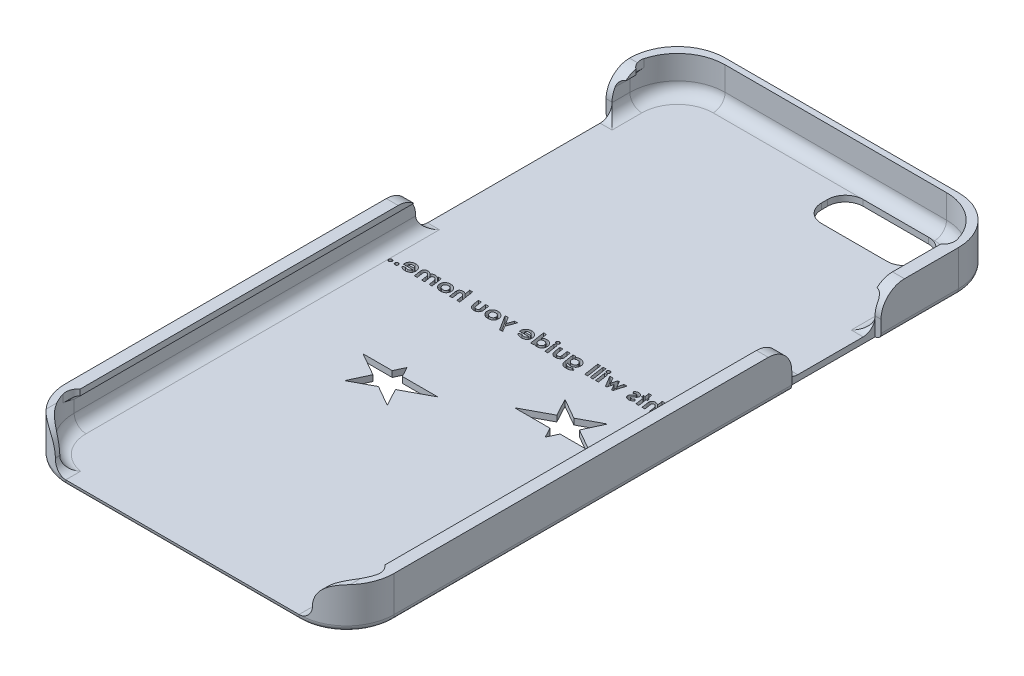
SolidWorks part; units mm, degrees
ref_plane "Front Plane" through (0, 0, 0) normal (0, 0, 1) x (1, 0, 0)
ref_plane "Top Plane" through (0, 0, 0) normal (0, 1, 0) x (1, 0, 0)
ref_plane "Right Plane" through (0, 0, 0) normal (1, 0, 0) x (0, 0, -1)
sketch "Sketch1" plane through (0, 0, 0) normal (0, 1, 0) x (1, 0, 0)
  line L1 (-35.052, 70.358) -> (35.052, 70.358)
  line L2 (-35.052, 70.358) -> (-35.052, -70.358)
  line L3 (-35.052, -70.358) -> (35.052, -70.358)
  line L4 (35.052, 70.358) -> (35.052, -70.358)
  line L5 (-35.052, 70.358) -> (35.052, -70.358) construction
  line L6 (-35.052, -70.358) -> (35.052, 70.358) construction
  point P0 (0, 0)
  dimension "D1" = 70.104
  dimension "D2" = 140.716
extrude "Boss-Extrude1" add sketch "Sketch1" along normal blind 1.27
sketch "Sketch2" plane through (0, 1.27, 0) normal (0, 1, 0) x (1, 0, 0)
  line L0 (-35.052, -70.358) -> (0, -70.358)
  line L1 (-35.052, -70.358) -> (35.052, -70.358) construction
  line L2 (-35.052, 70.358) -> (-35.052, -70.358)
  line L3 (-35.052, 70.358) -> (35.052, 70.358)
  line L4 (-33.782, 69.088) -> (-33.782, -69.088)
  line L5 (0, -70.358) -> (35.052, -70.358)
  line L6 (-33.782, -69.088) -> (33.782, -69.088)
  line L7 (35.052, 70.358) -> (35.052, -70.358)
  line L9 (33.782, 69.088) -> (33.782, -69.088)
  line L12 (-33.782, 69.088) -> (33.782, 69.088)
  dimension "D1" = 1.27
  dimension "D2" = 1.27
  dimension "D3" = 1.27
  dimension "D5" = 1.27
extrude "Boss-Extrude2" add sketch "Sketch2" along normal blind 7.62
sketch "Sketch3" plane through (-35.052, 0, 0) normal (-1, 0, 0) x (0, 0, 1)
  line L0 (-70.358, 8.89) -> (70.358, 8.89) construction
  line L1 (-55.118, 8.89) -> (-13.208, 8.89)
  line L2 (-55.118, 8.89) -> (-55.118, 1.27)
  line L3 (-55.118, 1.27) -> (-13.208, 1.27)
  line L4 (-13.208, 8.89) -> (-13.208, 1.27)
  line L5 (-70.358, 8.89) -> (-70.358, 0) construction
  line L6 (-70.358, 0) -> (70.358, 0) construction
  dimension "D1" = 15.24
  dimension "D2" = 57.15
  dimension "D3" = 1.27
extrude "Cut-Extrude1" cut sketch "Sketch3" against normal blind 1.27
sketch "Sketch5" plane through (35.052, 0, 0) normal (1, 0, 0) x (0, 0, -1)
  line L0 (-70.358, 8.89) -> (70.358, 8.89) construction
  line L1 (24.638, 8.89) -> (43.688, 8.89)
  line L2 (24.638, 8.89) -> (24.638, 1.27)
  line L3 (24.638, 1.27) -> (43.688, 1.27)
  line L4 (43.688, 8.89) -> (43.688, 1.27)
  line L5 (70.358, 8.89) -> (70.358, 0) construction
  line L6 (-70.358, 0) -> (70.358, 0) construction
  dimension "D1" = 26.67
  dimension "D2" = 45.72
  dimension "D3" = 1.27
extrude "Cut-Extrude2" cut sketch "Sketch5" against normal blind 1.27
sketch "Sketch6" plane through (0, 0, 70.358) normal (0, 0, 1) x (1, 0, 0)
  line L1 (-35.052, 8.89) -> (35.052, 8.89) construction
  line L2 (-27.432, 8.89) -> (27.432, 8.89)
  line L3 (-27.432, 8.89) -> (-27.432, 1.27)
  line L4 (-27.432, 1.27) -> (27.432, 1.27)
  line L8 (27.432, 8.89) -> (27.432, 1.27)
  line L9 (-35.052, 8.89) -> (-35.052, 0) construction
  line L10 (35.052, 8.89) -> (35.052, 0) construction
  line L11 (-35.052, 0) -> (35.052, 0) construction
  dimension "D1" = 7.62
  dimension "D2" = 7.62
  dimension "D3" = 1.27
extrude "Cut-Extrude3" cut sketch "Sketch6" against normal blind 1.27
sketch "Sketch7" plane through (0, 0, 0) normal (0, -1, 0) x (1, 0, 0)
  line L0 (35.052, 70.358) -> (35.052, -70.358) construction
  line L1 (26.162, -57.658) -> (4.572, -57.658)
  line L2 (26.162, -57.658) -> (26.162, -66.548)
  line L3 (26.162, -66.548) -> (4.572, -66.548)
  line L4 (4.572, -57.658) -> (4.572, -66.548)
  line L5 (35.052, -70.358) -> (-35.052, -70.358) construction
  dimension "D1" = 8.89
  dimension "D2" = 30.48
  dimension "D3" = 3.81
  dimension "D4" = 12.7
extrude "Cut-Extrude4" cut sketch "Sketch7" against normal blind 1.27
fillet "Fillet1" radius 10.16 4 edges at (33.782, 5.08, -69.088) (-33.782, 5.08, -69.088) (-33.782, 5.08, 69.088) (33.782, 5.08, 69.088)
fillet "Fillet2" radius 10.16 4 edges at (-35.052, 4.445, -70.358) (35.052, 4.445, -70.358) (35.052, 4.445, 70.358) (-35.052, 4.445, 70.358)
sketch "Sketch8" plane through (-33.782, 0, 0) normal (1, 0, 0) x (0, 0, -1)
  line L0 (58.928, 1.27) -> (58.928, 8.89) construction
  line L1 (55.118, 8.89) -> (58.928, 8.89)
  line L2 (55.118, 8.89) -> (55.118, 7.62)
  line L3 (55.118, 7.62) -> (58.928, 7.62)
  line L4 (58.928, 8.89) -> (58.928, 7.62)
  dimension "D1" = 1.27
extrude "Boss-Extrude3" add sketch "Sketch8" along normal blind 1.27
sketch "Sketch13" plane through (0, 0, -69.088) normal (0, 0, 1) x (1, 0, 0)
  line L0 (23.622, 1.27) -> (23.622, 8.89) construction
  line L1 (-23.622, 8.89) -> (23.622, 8.89)
  line L2 (-23.622, 8.89) -> (-23.622, 7.62)
  line L3 (-23.622, 7.62) -> (23.622, 7.62)
  line L4 (23.622, 8.89) -> (23.622, 7.62)
  dimension "D1" = 1.27
extrude "Boss-Extrude6" [suppressed] add sketch "Sketch13" along normal blind 1.27
sketch "Sketch14" plane through (33.782, 0, 0) normal (-1, 0, 0) x (0, 0, 1)
  line L0 (-43.688, 1.27) -> (-43.688, 8.89) construction
  line L1 (-58.928, 8.89) -> (-43.688, 8.89)
  line L2 (-58.928, 8.89) -> (-58.928, 7.62)
  line L3 (-58.928, 7.62) -> (-43.688, 7.62)
  line L4 (-43.688, 8.89) -> (-43.688, 7.62)
  dimension "D1" = 1.27
extrude "Boss-Extrude7" add sketch "Sketch14" along normal blind 1.27
sketch "Sketch19" plane through (33.782, 0, 0) normal (-1, 0, 0) x (0, 0, 1)
  line L1 (59.6694, 1.27) -> (59.6694, 8.89) construction
  line L2 (-24.638, 8.89) -> (59.6694, 8.89)
  line L3 (-24.638, 8.89) -> (-24.638, 7.62)
  line L4 (-24.638, 7.62) -> (59.6694, 7.62)
  line L5 (59.6694, 8.89) -> (59.6694, 7.62)
  dimension "D1" = 1.27
extrude "Boss-Extrude8" add sketch "Sketch19" along normal blind 1.27
sketch "Sketch20" plane through (-33.782, 0, 0) normal (1, 0, 0) x (0, 0, -1)
  line L1 (-59.6694, 8.89) -> (-59.6694, 1.27) construction
  line L2 (13.208, 8.89) -> (-59.6694, 8.89)
  line L3 (13.208, 8.89) -> (13.208, 7.62)
  line L4 (13.208, 7.62) -> (-59.6694, 7.62)
  line L5 (-59.6694, 8.89) -> (-59.6694, 7.62)
  dimension "D1" = 1.27
extrude "Boss-Extrude9" add sketch "Sketch20" along normal blind 1.27
fillet "Fillet9" radius 3.81 4 edges at (26.162, 0.635, -57.658) (26.162, 0.635, -66.548) (4.572, 0.635, -66.548) (4.572, 0.635, -57.658)
fillet "Fillet12" radius 1.27 8 edges at (32.0762, 0, 67.3822) (0, 0, 70.358) (-32.0762, 0, 67.3822) (-35.052, 0, 0) (-32.0762, 0, -67.3822) (0, 0, -70.358) (32.0762, 0, -67.3822) (35.052, 0, 0)
fillet "Fillet16" radius 2.54 9 edges at (33.782, 1.27, -51.308) (30.8062, 1.27, -66.1122) (-33.782, 1.27, -57.023) (-30.8062, 1.27, -66.1122) (33.782, 1.27, 17.5157) (-33.782, 1.27, 23.2307) (0, 1.27, -69.088) (32.0462, 1.27, 65.349) (-32.0462, 1.27, 65.349)
sketch "Sketch28" plane through (0, 1.27, 0) normal (0, 1, 0) x (1, 0, 0)
  line L0 (31.242, 24.638) -> (35.052, 24.638) construction
  line L1 (35.052, 43.688) -> (33.782, 43.688)
  line L2 (35.052, 43.688) -> (35.052, 24.638)
  line L3 (35.052, 24.638) -> (33.782, 24.638)
  line L4 (33.782, 43.688) -> (33.782, 24.638)
  line L5 (-31.242, 13.208) -> (-35.052, 13.208) construction
  line L6 (-35.052, 55.118) -> (-33.782, 55.118)
  line L7 (-35.052, 55.118) -> (-35.052, 13.208)
  line L8 (-35.052, 13.208) -> (-33.782, 13.208)
  line L9 (-33.782, 55.118) -> (-33.782, 13.208)
  dimension "D1" = 1.27
  dimension "D2" = 1.27
extrude "Cut-Extrude10" cut sketch "Sketch28" against normal blind 1.27
fillet "Fillet18" radius 1.27 4 edges at (33.782, 7.62, -51.308) (-33.782, 7.62, -57.023) (33.782, 7.62, 17.5157) (-33.782, 7.62, 23.2307)
fillet "Fillet28" radius 2.54 4 edges at (33.782, 7.62, 59.6694) (-33.782, 7.62, 59.6694) (33.782, 7.62, -58.928) (-33.782, 7.62, -58.928)
fillet "Fillet29" radius 5 6 edges at (27.432, 8.89, 69.5617) (-27.432, 8.89, 69.5617) (33.782, 8.89, -24.638) (33.782, 8.89, -43.688) (-33.782, 8.89, -13.208) (-33.782, 8.89, -55.118)
fillet "Fillet30" radius 2.54 6 edges at (-27.432, 1.27, 68.152) (27.432, 1.27, 68.152) (32.512, 1.27, -24.638) (32.512, 1.27, -43.688) (-32.512, 1.27, -13.208) (-32.512, 1.27, -55.118)
sketch "Sketch30" plane through (0, 0, 0) normal (0, -1, 0) x (-1, 0, 0)
  text T0 "<b><i>Lights will guide you home..</i></b>" font "Century Gothic" height 3.175
extrude "Cut-Extrude12" cut sketch "Sketch30" against normal blind 10
sketch "Sketch32" plane through (0, 0, 0) normal (0, -1, 0) x (-1, 0, 0)
  line L0 (-13.5259, -2.2191) -> (-15.5475, -5.9986)
  line L1 (-18.3867, -11.3068) -> (-19.3925, -9.1445)
  line L2 (-22.6136, -2.2191) -> (-17.915, -4.7323)
  line L3 (-9.6661, -9.1445) -> (-17.2302, -9.1445)
  line L4 (-25.6205, -9.1445) -> (-20.7023, -6.3283)
  line L5 (-17.915, -4.7323) -> (-13.5259, -2.2191)
  line L6 (-20.7023, -6.3283) -> (-22.6136, -2.2191)
  line L7 (-19.3925, -9.1445) -> (-25.6205, -9.1445)
  line L8 (-15.5475, -5.9986) -> (-9.6661, -9.1445)
  line L9 (-17.2302, -9.1445) -> (-18.3867, -11.3068)
  point P10 (0, 0)
  point P11 (0, 0)
  point P12 (0, 0)
sketch "Sketch35" plane through (0, 0, 0) normal (0, -1, 0) x (1, 0, 0)
  line L0 (-4.3761, 22.2588) -> (-6.3977, 18.4792)
  line L1 (-9.237, 13.1711) -> (-10.2427, 15.3334)
  line L2 (-13.4638, 22.2588) -> (-8.7652, 19.7456)
  line L3 (-0.5163, 15.3334) -> (-8.0804, 15.3334)
  line L4 (-16.4707, 15.3334) -> (-11.5525, 18.1495)
  line L5 (-8.7652, 19.7456) -> (-4.3761, 22.2588)
  line L6 (-11.5525, 18.1495) -> (-13.4638, 22.2588)
  line L7 (-10.2427, 15.3334) -> (-16.4707, 15.3334)
  line L8 (-6.3977, 18.4792) -> (-0.5163, 15.3334)
  line L9 (-8.0804, 15.3334) -> (-9.237, 13.1711)
  point P10 (9.1498, -13.6168)
  point P11 (9.1498, -13.6168)
  point P12 (9.1498, -13.6168)
  point P13 (0, 0)
extrude "Cut-Extrude15" cut sketch "Sketch32" against normal blind 20
extrude "Cut-Extrude16" cut sketch "Sketch35" against normal blind 20
